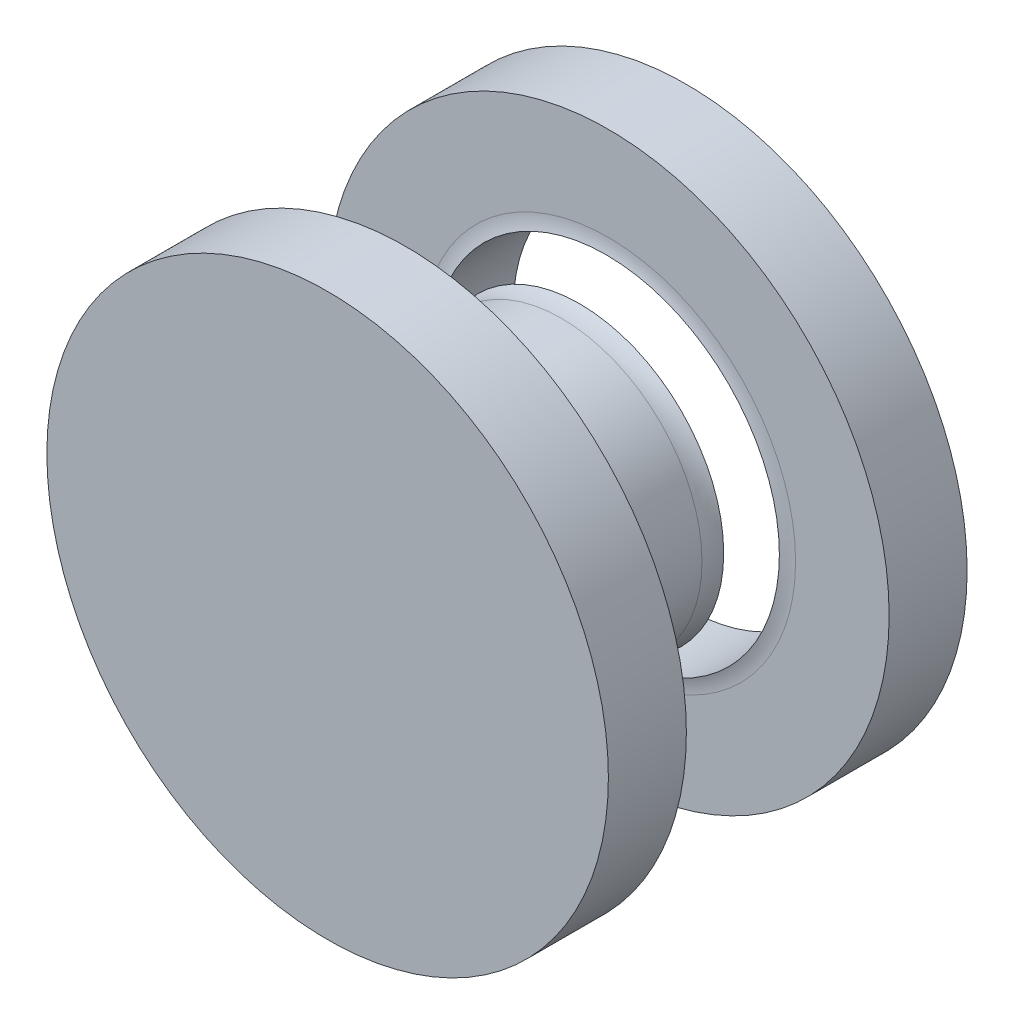
SolidWorks part; units mm, degrees
material "Plain Carbon Steel"
ref_plane "Front Plane" through (0, 0, 0) normal (1, 0, 0) x (0, 1, 0)
ref_plane "Top Plane" through (0, 0, 0) normal (0, 0, 1) x (0, 1, 0)
ref_plane "Right Plane" through (0, 0, 0) normal (0, 1, 0) x (-1, 0, 0)
sketch "Sketch1" plane through (0, 0, 0) normal (0, 0, 1) x (0, 1, 0)
  circle A0 centre (0, 0) radius 18
  dimension "D1" = 36
extrude "Boss-Extrude1" add sketch "Sketch1" along normal blind 5
sketch "Sketch3" plane through (0, 0, 5) normal (0, 0, 1) x (1, 0, 0)
  circle A0 centre (0, 0) radius 9
  dimension "D1" = 18
sketch "Sketch5" plane through (0, 0, 0) normal (0, 0, -1) x (1, 0, 0)
  circle A0 centre (0, 0) radius 5.35
  dimension "D1" = 10.7
extrude "Boss-Extrude2" add sketch "Sketch3" along normal blind 6.5
ref_plane "Plane1" through (0, 0, 11.5) normal (0, 0, 1) x (0, -1, 0)
fillet "Fillet8" radius 3 1 edges at (9, 0, 5) type face fillet first side face at (9, 0, 11.5) second side face at (9, 0, 5)
mirror "Mirror2" about plane through (0, 0, 11.5) normal (0, 0, 1) of bodies 115
sketch "Sketch9" plane through (0, 0, 0) normal (0, 0, -1) x (1, 0, 0)
  circle A0 centre (0, 0) radius 11.1
  dimension "D1" = 11.1
extrude "Cut-Extrude6" cut sketch "Sketch9" against normal blind 6.84
